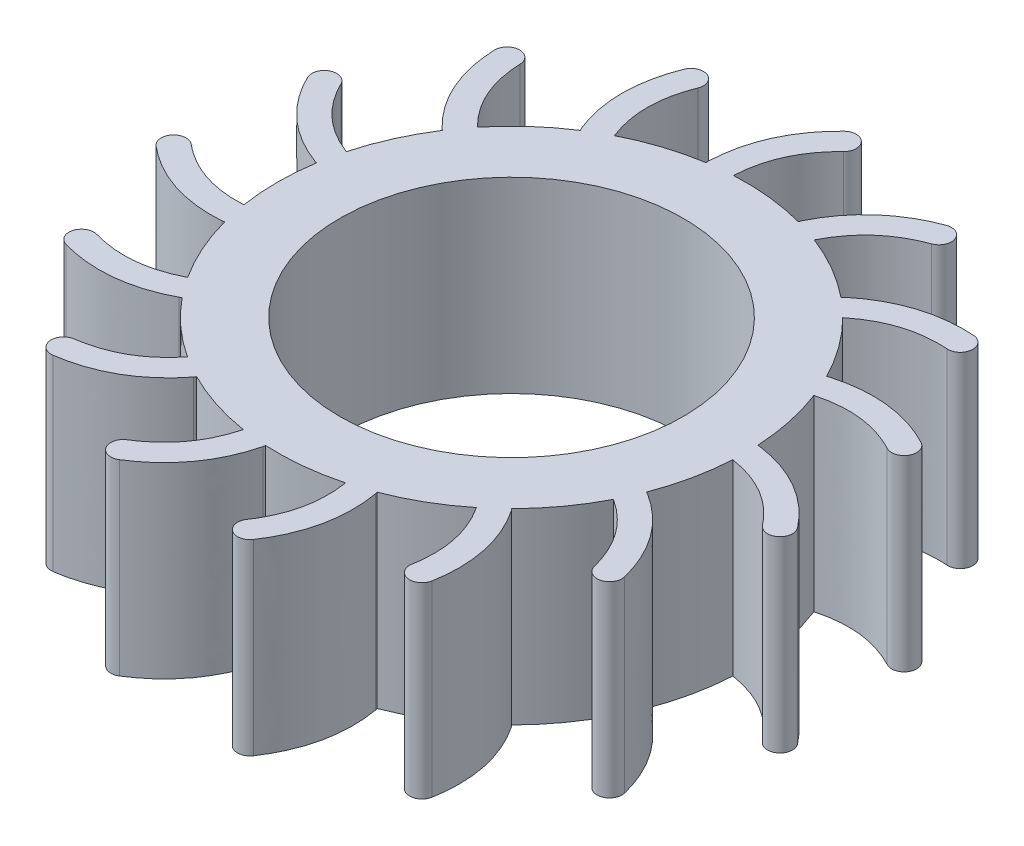
SolidWorks part; units mm, degrees
ref_plane "Front Plane" through (0, 0, 0) normal (0, 0, 1) x (1, 0, 0)
ref_plane "Top Plane" through (0, 0, 0) normal (0, 1, 0) x (1, 0, 0)
ref_plane "Right Plane" through (0, 0, 0) normal (1, 0, 0) x (0, 0, -1)
sketch "Sketch1" plane through (0, 0, 0) normal (0, 1, 0) x (1, 0, 0)
  circle A0 centre (0, 0) radius 13.75
  circle A2 centre (0, 0) radius 18.75
  dimension "D1" = 27.5
  dimension "D2" = 5
extrude "Boss-Extrude1" add sketch "Sketch1" along normal blind 15
sketch "Sketch2" plane through (0, 0, 0) normal (0, 1, 0) x (1, 0, 0)
  line L0 (18.75, 0) -> (18.75, -4.8789) construction
  line L1 (18.6074, -0.9898) -> (18.5624, -0.9833)
  line L2 (18.5624, -0.9833) -> (18.5624, 0.9898)
  line L3 (18.75, 0) -> (25.2452, -3.75) construction
  line L4 (21.9976, -1.875) -> (22.3726, -1.2255) construction
  line L5 (18.5624, 0.9898) -> (18.8926, 0.9898)
  circle A0 centre (0, 0) radius 18.75 construction
  circle A1 centre (0, 0) radius 18.75
  arc A3 (26.0311, -3.1316) -> (24.4593, -4.3684) centre (25.2452, -3.75) cw
  spline S0 degree 2 poles (18.75, 0) (22.7476, -0.576) (25.2452, -3.75) knots 0 0 0 1 1 1 construction
  spline S1 degree 1 poles (18.6074, -0.9898) (24.4593, -4.3684) knots 0 0 1 1 construction
  spline S2 degree 2 poles (18.6074, -0.9898) (19.9749, -1.1886) (21.8935, -2.0554) (23.6034, -3.2834) (24.4593, -4.3684) knots 0 0 0 0.375 0.625 1 1 1
  spline S3 degree 1 poles (18.8926, 0.9898) (26.0311, -3.1316) knots 0 0 1 1 construction
  spline S4 degree 2 poles (18.8926, 0.9898) (20.5232, 0.7566) (22.8986, -0.3144) (25.0138, -1.836) (26.0311, -3.1316) knots 0 0 0 0.375 0.625 1 1 1
  point P16 (0, 0)
  dimension "D3" = 60
  dimension "D1" = 0.75
  dimension "D2" = 7.5
  dimension "D4" = 1
  dimension "D5" = 1
extrude "Boss-Extrude2" add sketch "Sketch2" along normal up to surface (15 mm away) contours S4 A1 L1 S2 A3 region at (22.5584, 0, 1.6581) up to face at (0, 15, 18.75)
pattern_circular "CirPattern1" count 15 over 360 about axis through (0, 15, 0) along (0, 1, 0) of "Boss-Extrude2"
